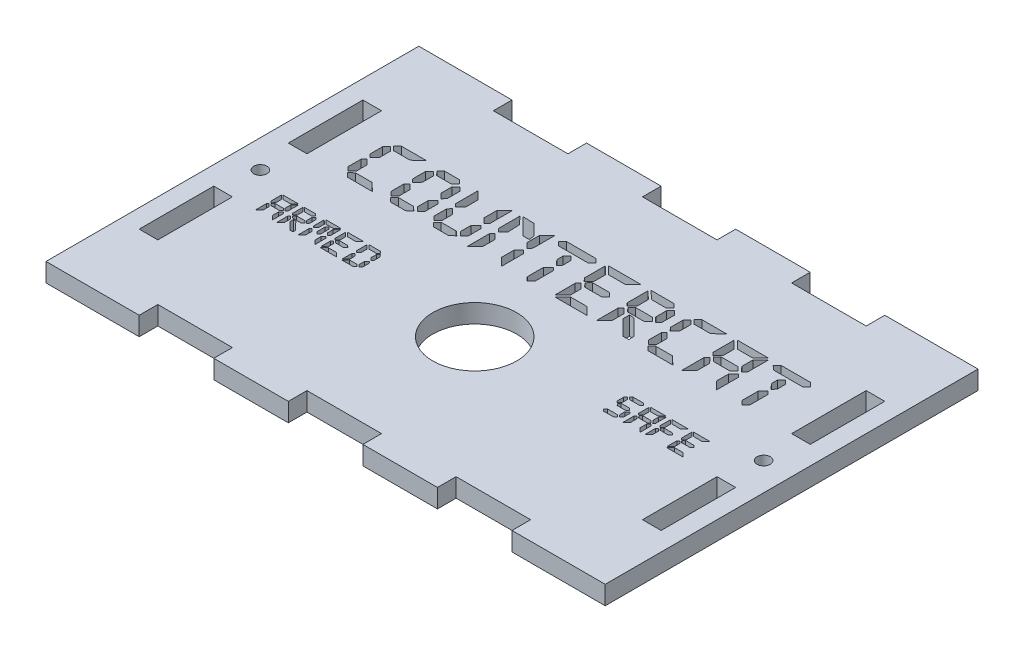
SolidWorks part; units mm, degrees
ref_plane "Front Plane" through (0, 0, 0) normal (0, 0, 1) x (1, 0, 0)
ref_plane "Top Plane" through (0, 0, 0) normal (0, 1, 0) x (1, 0, 0)
ref_plane "Right Plane" through (0, 0, 0) normal (1, 0, 0) x (0, 0, -1)
sketch "Sketch1" plane through (0, 0, 0) normal (0, 1, 0) x (1, 0, 0)
  line L1 (0, 0) -> (190.5, 0)
  line L2 (0, 0) -> (0, 127)
  line L3 (0, 127) -> (190.5, 127)
  line L4 (190.5, 0) -> (190.5, 127)
  dimension "D1" = 127
  dimension "D2" = 190.5
extrude "Boss-Extrude1" add sketch "Sketch1" along normal blind 6.35
sketch "Sketch13" plane through (0, 6.35, 0) normal (0, 1, 0) x (1, 0, 0)
  line L0 (0, 0) -> (190.5, 0) construction
  line L1 (31.75, 0) -> (57.15, 0)
  line L2 (31.75, 0) -> (31.75, 6.35)
  line L3 (31.75, 6.35) -> (57.15, 6.35)
  line L4 (57.15, 0) -> (57.15, 6.35)
  line L5 (82.55, 6.35) -> (107.95, 6.35)
  line L6 (107.95, 0) -> (107.95, 6.35)
  line L7 (82.55, 0) -> (107.95, 0)
  line L8 (82.55, 0) -> (82.55, 6.35)
  line L9 (133.35, 6.35) -> (158.75, 6.35)
  line L10 (158.75, 0) -> (158.75, 6.35)
  line L11 (133.35, 0) -> (158.75, 0)
  line L12 (133.35, 0) -> (133.35, 6.35)
  line L17 (31.75, 6.35) -> (82.55, 6.35) construction
  line L18 (0, 127) -> (0, 0) construction
  dimension "D1" = 25.4
  dimension "D2" = 6.35
  dimension "D4" = 50.8
  dimension "D5" = 31.75
  dimension "D3" = 3
extrude "Cut-Extrude6" cut sketch "Sketch13" against normal blind 6.35
pattern_linear "LPattern7" count 2 spacing 120.65 along (0, 0, -1) of "Cut-Extrude6"
sketch "Sketch14" plane through (0, 6.35, 0) normal (0, 1, 0) x (1, 0, 0)
  line L0 (0, 127) -> (0, 0) construction
  line L1 (6.35, 25.4) -> (12.7, 25.4)
  line L2 (6.35, 25.4) -> (6.35, 50.8)
  line L3 (6.35, 50.8) -> (12.7, 50.8)
  line L4 (12.7, 25.4) -> (12.7, 50.8)
  line L5 (0, 0) -> (31.75, 0) construction
  line L6 (177.8, 50.8) -> (184.15, 50.8)
  line L7 (177.8, 25.4) -> (177.8, 50.8)
  line L8 (184.15, 25.4) -> (184.15, 50.8)
  line L9 (177.8, 25.4) -> (184.15, 25.4)
  line L10 (177.8, 101.6) -> (184.15, 101.6)
  line L11 (177.8, 76.2) -> (177.8, 101.6)
  line L12 (184.15, 76.2) -> (184.15, 101.6)
  line L13 (177.8, 76.2) -> (184.15, 76.2)
  line L14 (6.35, 101.6) -> (12.7, 101.6)
  line L15 (6.35, 76.2) -> (6.35, 101.6)
  line L16 (12.7, 76.2) -> (12.7, 101.6)
  line L17 (6.35, 76.2) -> (12.7, 76.2)
  dimension "D1" = 25.4
  dimension "D2" = 6.35
  dimension "D3" = 6.35
  dimension "D4" = 25.4
  dimension "D5" = 2
  dimension "D6" = 2
extrude "Cut-Extrude7" cut sketch "Sketch14" against normal blind 6.35
hole_wizard "#8 Clearance Hole1" positions "Sketch16" profile "Sketch15" hole size "#8" standard "ANSI Inch"
sketch "Sketch16" plane through (0, 6.35, 0) normal (0, 1, 0) x (1, 0, 0)
  line L0 (12.7, 50.8) -> (6.35, 50.8) construction
  line L1 (6.35, 50.8) -> (6.35, 25.4) construction
  line L2 (184.15, 50.8) -> (177.8, 50.8) construction
  line L3 (177.8, 50.8) -> (177.8, 25.4) construction
  point P0 (9.525, 63.5)
  point P3 (9.525, 50.8)
  point P8 (180.975, 63.5)
  dimension "D1" = 12.7
  dimension "D2" = 3.175
  dimension "D3" = 12.7
  dimension "D4" = 3.175
sketch "Sketch15" plane through (9.525, 6.35, -63.5) normal (1, 0, 0) x (0, 0, 1)
  line L0 (0, 0) -> (0, 11.5107)
  line L1 (0, 11.5107) -> (2.2479, 10.16)
  line L2 (2.2479, 10.16) -> (2.2479, 0)
  line L5 (2.2479, 0) -> (0, 0)
  line L10 (0, 11.5107) -> (-2.2479, 10.16) construction
  line L11 (0, -6.35) -> (0, 107.95) construction
  dimension "Hole Dia." = 4.4958
  dimension "Hole Depth" = 10.16
  dimension "Drill Angle" = 118
sketch "Sketch18" plane through (0, 6.35, 0) normal (0, 1, 0) x (1, 0, 0)
  line L0 (0, 127) -> (0, 0) construction
  line L1 (107.95, 6.35) -> (82.55, 6.35) construction
  circle A0 centre (95.25, 50.8) radius 14.2875
  dimension "D1" = 28.575
  dimension "D2" = 95.25
  dimension "D3" = 44.45
extrude "Cut-Extrude9" cut sketch "Sketch18" against normal blind 7.62
sketch "Sketch19" plane through (0, 6.35, 0) normal (0, 1, 0) x (1, 0, 0)
  line L0 (12.7, 76.2) -> (177.8, 76.2)
  line L3 (12.7, 101.6) -> (6.35, 101.6) construction
  dimension "D1" = 25.4
sketch "Sketch20" plane through (0, 6.35, 0) normal (0, 1, 0) x (1, 0, 0)
  text T0 "Countercat" font "DS-Digital" height in points 72
extrude "Cut-Extrude10" cut sketch "Sketch20" against normal blind 10.16
sketch "Sketch21" plane through (0, 6.35, 0) normal (0, 1, 0) x (1, 0, 0)
  line L0 (12.7, 50.8) -> (63.5, 50.8)
  line L2 (177.8, 50.8) -> (127, 50.8)
  circle A0 centre (95.25, 50.8) radius 14.2875 construction
  dimension "D1" = 50.8
  dimension "D2" = 50.8
  dimension "D3" = 0
  dimension "D4" = 0
sketch "Sketch22" plane through (0, 6.35, 0) normal (0, 1, 0) x (1, 0, 0)
  text T0 "armed" font "DS-Digital" height in points 36
  text T1 "Safe" font "DS-Digital" height in points 36
extrude "Cut-Extrude11" cut sketch "Sketch22" against normal blind 10.16
equation "\"THICK\"= .25"
